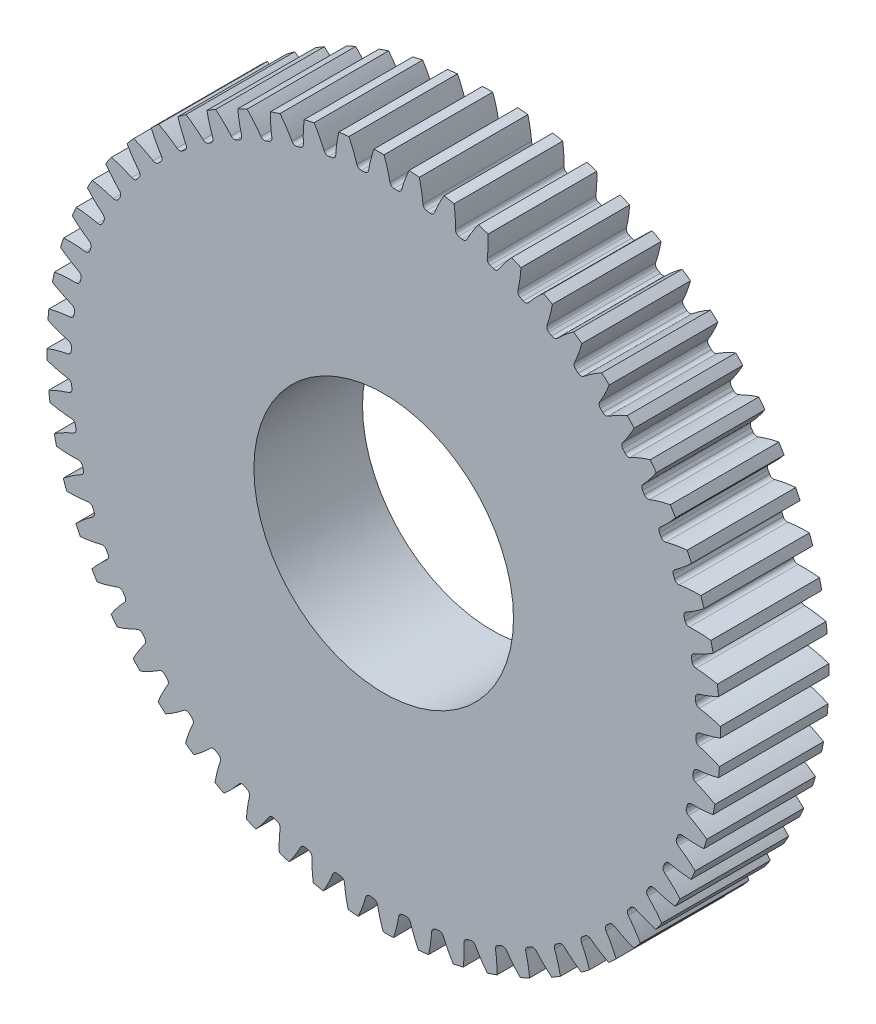
SolidWorks part; units mm, degrees
ref_plane "Front" through (0, 0, 0) normal (0, 0, 1) x (1, 0, 0)
ref_plane "Top" through (0, 0, 0) normal (0, 1, 0) x (1, 0, 0)
ref_plane "Right" through (0, 0, 0) normal (1, 0, 0) x (0, 0, -1)
sketch "Sketch3" plane through (0, 0, 0) normal (0, 0, 1) x (1, 0, 0)
  circle A0 centre (0, 0) radius 78.74
  dimension "od" = 157.48
extrude "gearBody" add sketch "Sketch3" along normal blind 25.4
sketch "Sketch2" plane through (0, 0, 0) normal (0, 0, 1) x (1, 0, 0)
  line L0 (0, 0) -> (68.1572, 28.2316) construction
  line L1 (92.002, -18.3096) -> (0, 0) construction
  line L2 (0, 0) -> (36.3143, 0) construction
  line L3 (76.1945, -0.916) -> (76.0401, -4.9343) construction
  line L5 (76.1173, -2.9252) -> (0, 0) construction
  line L7 (0, 0) -> (73.7729, 0) construction
  arc A0 (73.758, -1.4806) -> (73.6541, -4.1844) centre (0, 0) ccw construction
  arc A1 (78.7399, -0.0913) -> (78.5147, -5.9519) centre (0, 0) ccw construction
  arc A2 (76.1945, -0.916) -> (76.0401, -4.9343) centre (0, 0) ccw construction
  arc A3 (73.031, -3.2028) -> (73.0614, -2.4115) centre (0, 0) ccw
  arc A4 (92.002, -18.3096) -> (73.7695, -4.2158) centre (65.7895, -33.3792) ccw
  arc A5 (92.002, -18.3096) -> (93.1358, 11.1948) centre (0, 0) ccw
  arc A6 (93.1358, 11.1948) -> (73.8754, -1.4582) centre (68.1572, 28.2316) cw
  arc A7 (73.0614, -2.4115) -> (73.8754, -1.4582) centre (74.0654, -2.4446) cw
  arc A8 (73.7695, -4.2158) -> (73.031, -3.2028) centre (74.0346, -3.2468) cw
  point P6 (93.1358, 11.1948)
  point P22 (92.002, -18.3096)
  dimension "baseDia" = 147.5457
  dimension "od" = 157.48
  dimension "pd" = 152.4
  dimension "rd" = 146.2024
  dimension "rFillet" = 1.0046
  dimension "pointX" = 93.1358
  dimension "pointY" = 11.1948
  dimension "CTT" = 4.0183
  dimension "flankCenterAngle" = 22.5
extrude "toothCut" cut sketch "Sketch2" along normal through all
pattern_circular "CirPattern1" count 60 over 360 about axis through (0, 0, 25.4) along (0, 0, -1) of "toothCut"
ref_axis "toothSpace" through (0, 0, 0) along (0.9993, -0.0384, 0)
ref_axis "Axis2" through (78.4158, -7.1375, 0) along (-0.9959, 0.0906, 0)
sketch "hub1Dia" plane through (0, 0, 0) normal (0, 0, -1) x (-1, 0, 0)
  circle A0 centre (0, 0) radius 12.7
  dimension "hub1Dia" = 25.4
sketch "hub2Dia" plane through (0, 0, 25.4) normal (0, 0, 1) x (1, 0, 0)
  circle A0 centre (0, 0) radius 12.7
  dimension "hub2dia" = 25.4
sketch "boreDia" plane through (0, 0, 0) normal (0, 0, 1) x (1, 0, 0)
  circle A0 centre (0, 0) radius 30.353
  dimension "boreDia" = 60.706
extrude "bore" cut sketch "boreDia" against normal mid plane 25400
sketch "kwy1sketch" plane through (0, 0, 0) normal (0, 0, 1) x (1, 0, 0)
  line L0 (-5.3333, 0.3917) -> (0, 0) construction
  line L1 (56.5335, 8.5819) -> (54.6729, -16.7499)
  line L2 (54.6729, -16.7499) -> (23.0082, -14.4241)
  line L3 (56.5335, 8.5819) -> (24.8688, 10.9076)
  line L4 (23.0082, -14.4241) -> (0, 0)
  line L5 (0, 0) -> (24.8688, 10.9076)
  line L6 (0, 0) -> (73.0473, -2.8072) construction
  line L7 (55.6032, -4.084) -> (0, 0) construction
  arc A7 (73.031, -3.2028) -> (73.0614, -2.4115) centre (0, 0) ccw construction
  point P9 (55.6032, -4.084)
  point P13 (-0.8897, 0.0653)
  dimension "kwy1width" = 25.4
  dimension "kwy1depth" = 55.753
  dimension "kwy1angle" = 2
  dimension "kwy1Depth2" = 31.75
sketch "kwy2sketch" plane through (0, 0, 0) normal (0, 0, 1) x (1, 0, 0)
  line L0 (73.0473, -2.8072) -> (0, 0) construction
  line L1 (0, 0) -> (-2.7975, -2.4146) construction
  line L2 (33.9069, 46.0435) -> (50.5036, 26.8156)
  line L3 (50.5036, 26.8156) -> (26.4687, 6.0699)
  line L4 (33.9069, 46.0435) -> (9.8721, 25.2978)
  line L5 (26.4687, 6.0699) -> (0, 0)
  line L6 (0, 0) -> (9.8721, 25.2978)
  arc A2 (73.031, -3.2028) -> (73.0614, -2.4115) centre (0, 0) ccw construction
  point P10 (42.2052, 36.4296)
  dimension "kwy2angle" = 43
  dimension "kwy2Width" = 25.4
  dimension "kwy2depth" = 55.753
  dimension "kwy2Depth2" = 31.75
sketch "kwy3sketch" plane through (0, 0, 0) normal (0, 0, 1) x (1, 0, 0)
  line L0 (73.0473, -2.8072) -> (0, 0) construction
  line L1 (0, 0) -> (-0.1958, -2.6663) construction
  line L2 (-8.5819, 56.5335) -> (16.7499, 54.6729)
  line L3 (16.7499, 54.6729) -> (14.4241, 23.0082)
  line L4 (-8.5819, 56.5335) -> (-10.9076, 24.8688)
  line L5 (14.4241, 23.0082) -> (0, 0)
  line L6 (-10.9076, 24.8688) -> (0, 0)
  point P10 (4.084, 55.6032)
  dimension "kwy3angle" = 88
  dimension "kwy3depth" = 55.753
  dimension "kwy3width" = 25.4
  dimension "kwy3Depth2" = 31.75
sketch "kwy4sketch" plane through (0, 0, 0) normal (0, 0, 1) x (1, 0, 0)
  line L0 (73.0473, -2.8072) -> (0, 0) construction
  line L1 (0, 0) -> (1.3659, -1.5824) construction
  line L2 (-26.8156, 50.5036) -> (-46.0435, 33.9069)
  line L3 (-46.0435, 33.9069) -> (-25.2978, 9.8721)
  line L4 (-25.2978, 9.8721) -> (0, 0)
  line L5 (-6.0699, 26.4687) -> (0, 0)
  line L6 (-26.8156, 50.5036) -> (-6.0699, 26.4687)
  point P15 (-36.4296, 42.2052)
  dimension "kwy4angle" = 133
  dimension "kwy4depth" = 55.753
  dimension "kwy4width" = 25.4
  dimension "kwy4Depth2" = 31.75
sketch "kwy5sketch" plane through (0, 0, 0) normal (0, 0, 1) x (1, 0, 0)
  line L0 (73.0473, -2.8072) -> (0, 0) construction
  line L1 (0, 0) -> (1.7905, -0.1315) construction
  line L2 (-54.6729, 16.7499) -> (-56.5335, -8.5819)
  line L3 (-56.5335, -8.5819) -> (-24.8688, -10.9076)
  line L4 (-54.6729, 16.7499) -> (-23.0082, 14.4241)
  line L5 (-24.8688, -10.9076) -> (0, 0)
  line L6 (-23.0082, 14.4241) -> (0, 0)
  point P10 (-55.6032, 4.084)
  dimension "kwy5width" = 25.4
  dimension "kwy5depth" = 55.753
  dimension "kwy5angle" = 178
  dimension "kwy5Depth2" = 31.75
sketch "kwy6sketch" plane through (0, 0, 0) normal (0, 0, 1) x (1, 0, 0)
  line L0 (73.0473, -2.8072) -> (0, 0) construction
  line L1 (0, 0) -> (1.358, 1.1721) construction
  line L2 (-50.5036, -26.8156) -> (-33.9069, -46.0435)
  line L3 (-33.9069, -46.0435) -> (-9.8721, -25.2978)
  line L4 (-50.5036, -26.8156) -> (-26.4687, -6.0699)
  line L5 (-9.8721, -25.2978) -> (0, 0)
  line L6 (-26.4687, -6.0699) -> (0, 0)
  point P10 (-42.2052, -36.4296)
  dimension "kwy6angle" = 223
  dimension "kwy6width" = 25.4
  dimension "kwy6depth" = 55.753
  dimension "kwy6Depth2" = 31.75
sketch "kwy7sketch" plane through (0, 0, 0) normal (0, 0, 1) x (1, 0, 0)
  line L0 (73.0473, -2.8072) -> (0, 0) construction
  line L1 (0, 0) -> (0.1472, 2.0043) construction
  line L2 (-16.7499, -54.6729) -> (8.5819, -56.5335)
  line L3 (-16.7499, -54.6729) -> (-14.4241, -23.0082)
  line L4 (8.5819, -56.5335) -> (10.9076, -24.8688)
  line L5 (-14.4241, -23.0082) -> (0, 0)
  line L6 (10.9076, -24.8688) -> (0, 0)
  point P10 (-4.084, -55.6032)
  dimension "kwy7angle" = 88
  dimension "kwy7width" = 25.4
  dimension "kwy7depth" = 55.753
  dimension "kwy7angle1" = 268
  dimension "kwy7Depth2" = 31.75
sketch "kwy8sketch" plane through (0, 0, 0) normal (0, 0, 1) x (1, 0, 0)
  line L0 (73.0473, -2.8072) -> (0, 0) construction
  line L1 (0, 0) -> (-1.1667, 1.3516) construction
  line L2 (26.8156, -50.5036) -> (46.0435, -33.9069)
  line L3 (46.0435, -33.9069) -> (25.2978, -9.8721)
  line L4 (26.8156, -50.5036) -> (6.0699, -26.4687)
  line L5 (25.2978, -9.8721) -> (0, 0)
  line L6 (6.0699, -26.4687) -> (0, 0)
  point P10 (36.4296, -42.2052)
  dimension "kwy8angle" = 313
  dimension "kwy8width" = 25.4
  dimension "kwy8depth" = 55.753
  dimension "kwy8Depth2" = 31.75
sketch "centerLine" plane through (0, 0, 0) normal (0, 1, 0) x (1, 0, 0)
  line L0 (0, 36.4807) -> (0, -59.6309) construction
ref_plane "CB1plane" through (0, 0, 0) normal (0, 0, -1) x (-1, 0, 0)
sketch "CB1diameter" plane through (0, 0, 0) normal (0, 0, -1) x (-1, 0, 0)
  circle A0 centre (0, 0) radius 12.7
  dimension "CB1diameter" = 25.4
ref_plane "CB2plane" through (0, 0, 25.4) normal (0, 0, 1) x (1, 0, 0)
sketch "CB2diameter" plane through (0, 0, 25.4) normal (0, 0, 1) x (1, 0, 0)
  circle A0 centre (0, 0) radius 12.7
  dimension "CB2diameter" = 25.4
ref_axis "Axis1" through (0, 0, 50) along (0, 0, -1)
sketch3d "3DSketch1" plane through (0, 0, 0) normal (0, 0, 1) x (1, 0, 0)
